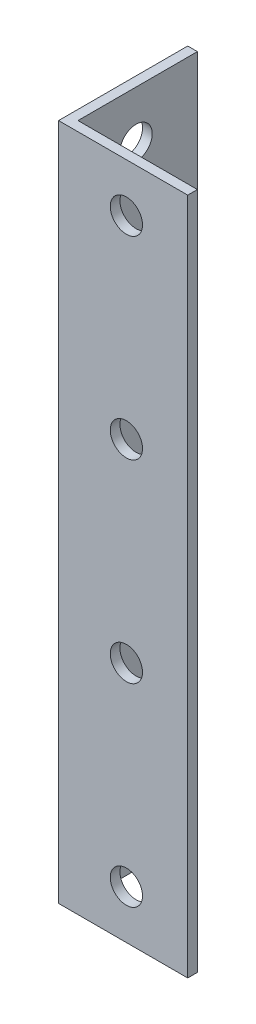
SolidWorks part; units mm, degrees
ref_plane "Спереди" through (0, 0, 0) normal (0, 0, 1) x (1, 0, 0)
ref_plane "Сверху" through (0, 0, 0) normal (0, 1, 0) x (1, 0, 0)
ref_plane "Справа" through (0, 0, 0) normal (1, 0, 0) x (0, 0, -1)
sketch "Эскиз1" plane through (0, 0, 0) normal (0, 1, 0) x (1, 0, 0)
  line L0 (0, 40) -> (0, 0)
  line L1 (0, 0) -> (40, 0)
  dimension "D1" = 40
extrude "Вытянуть-Тонкостенный1" add sketch "Эскиз1" along normal blind 210 thin thin type one direction reverse wall 3
sketch "Эскиз2" plane through (0, 0, 0) normal (-1, 0, 0) x (0, 0, 1)
  circle A0 centre (-21, 15) radius 5
  circle A1 centre (-21, 75) radius 5
  circle A6 centre (-21, 135) radius 5
  circle A7 centre (-21, 195) radius 5
  dimension "D1" = 4
extrude "Вырез-Вытянуть1" cut sketch "Эскиз2" against normal through all
sketch "Эскиз3" plane through (0, 0, 0) normal (0, 0, 1) x (1, 0, 0)
  circle A0 centre (21, 15) radius 5
  circle A1 centre (21, 75) radius 5
  circle A4 centre (21, 135) radius 5
  circle A5 centre (21, 195) radius 5
  dimension "D1" = 4
extrude "Вырез-Вытянуть2" cut sketch "Эскиз3" against normal through all
